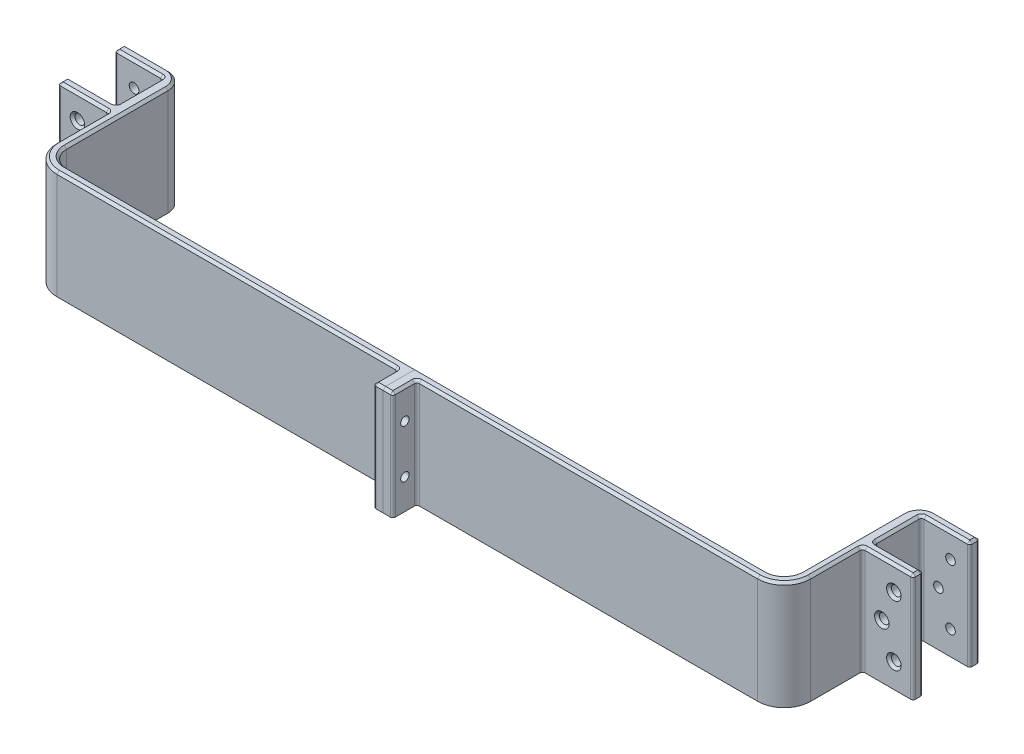
SolidWorks part; units mm, degrees
ref_plane "Front" through (0, 0, 0) normal (0, 0, 1) x (1, 0, 0)
ref_plane "Top" through (0, 0, 0) normal (0, 1, 0) x (1, 0, 0)
ref_plane "Right" through (0, 0, 0) normal (1, 0, 0) x (0, 0, -1)
sketch "Sketch1" plane through (0, 0, 0) normal (0, 1, 0) x (1, 0, 0)
  line L1 (-152.4, 0) -> (-152.4, 56)
  line L2 (-152.4, 56) -> (-177.4, 56)
  line L3 (-177.4, 56) -> (-177.4, 52)
  line L4 (-177.4, 52) -> (-157.4, 52)
  line L5 (-157.4, 52) -> (-157.4, 32.5)
  line L6 (-157.4, 32.5) -> (-177.4, 32.5)
  line L7 (-177.4, 32.5) -> (-177.4, 28.5)
  line L8 (-177.4, 28.5) -> (-156.4, 28.5)
  line L9 (-156.4, 28.5) -> (-156.4, -4)
  line L11 (0, 126.7654) -> (0, -150.0124) construction
  line L22 (0, -14) -> (0, 0)
  line L23 (0, 0) -> (-152.4, 0)
  line L24 (0, -14) -> (-4, -14)
  line L25 (-4, -14) -> (-4, -4)
  line L26 (-4, -4) -> (-156.4, -4)
  point P16 (0, -14)
  point P25 (0, 0)
  dimension "D1" = 304.8
  dimension "D2" = 4
  dimension "D3" = 4
  dimension "D4" = 5
  dimension "D5" = 19.5
  dimension "D6" = 4
  dimension "D7" = 20
  dimension "D8" = 4
  dimension "D9" = 10
  dimension "D10" = 60
extrude "Boss-Extrude1" add sketch "Sketch1" along normal mid plane 45
sketch "Sketch4" plane through (0, 0, -28.5) normal (0, 0, 1) x (1, 0, 0)
  line L0 (0, 0) -> (-119.7332, 0) construction
  line L1 (0, 22.5) -> (0, -22.5) construction
  line L2 (-156.4, 22.5) -> (-156.4, -22.5) construction
  circle A0 centre (-164.4, 0) radius 2
  circle A1 centre (-169.4, 12.5) radius 2
  circle A2 centre (-169.4, -12.5) radius 2
  point P10 (0, 0)
  dimension "D1" = 4
  dimension "D2" = 8
  dimension "D3" = 5
  dimension "D4" = 25
extrude "Cut-Extrude1" cut sketch "Sketch4" against normal through all
sketch "Sketch5" plane through (-4, 0, 0) normal (-1, 0, 0) x (0, 0, 1)
  line L0 (0, 0) -> (26.957, 0) construction
  line L1 (4, 22.5) -> (4, -22.5) construction
  circle A0 centre (9, 10) radius 1.75
  circle A1 centre (9, -10) radius 1.75
  point P7 (0, 0)
  dimension "D1" = 3.5
  dimension "D2" = 20
  dimension "D3" = 5
extrude "Cut-Extrude2" cut sketch "Sketch5" against normal through all
fillet "Fillet1" radius 7 2 edges at (-152.4, 0, -56) (-152.4, 0, 0)
fillet "Fillet3" radius 11 1 edges at (-156.4, 0, 4)
fillet "Fillet2" radius 1 9 edges at (-156.4, 0, -28.5) (-177.4, 0, -32.5) (-157.4, 0, -32.5) (-157.4, 0, -52) (-177.4, 0, -52) (-177.4, 0, -56) (-177.4, 0, -28.5) (-4, 0, 14) (-4, 0, 4)
chamfer "Chamfer1" distance 1 angle 45 25 edges at (-156.4, 22.5, -17.25) (-156.6929, 22.5, -28.2071) (-166.9, 22.5, -28.5) (-177.1071, 22.5, -28.7929) (-177.4, 22.5, -30.5) (-177.1071, 22.5, -32.2071) (-167.4, 22.5, -32.5) (-157.6929, 22.5, -32.7929) (-157.4, 22.5, -42.25) (-157.6929, 22.5, -51.7071) (-167.4, 22.5, -52) (-177.1071, 22.5, -52.2929) (-152.4, 22.5, -28) (-177.4, 22.5, -54) (-154.4503, 22.5, -53.9497) (-177.1071, 22.5, -55.7071) (-167.9, 22.5, -56) (-72.7, 22.5, 0) (-150.3497, 22.5, -2.0503) (-75.2, 22.5, 4) (-1.5, 22.5, 14) (-3.7071, 22.5, 13.7071) (-4, 22.5, 9) (-4.2929, 22.5, 4.2929) (-153.1782, 22.5, 0.7782)
chamfer "Chamfer2" distance 1 angle 45 6 edges at (-167.4, 12.5, -56) (-162.4, 0, -56) (-167.4, -12.5, -56) (-167.4, -12.5, -28.5) (-162.4, 0, -28.5) (-167.4, 12.5, -28.5)
mirror "Mirror1" about plane through (0, 22.5, 14) normal (-1, 0, 0) of bodies 104 101
